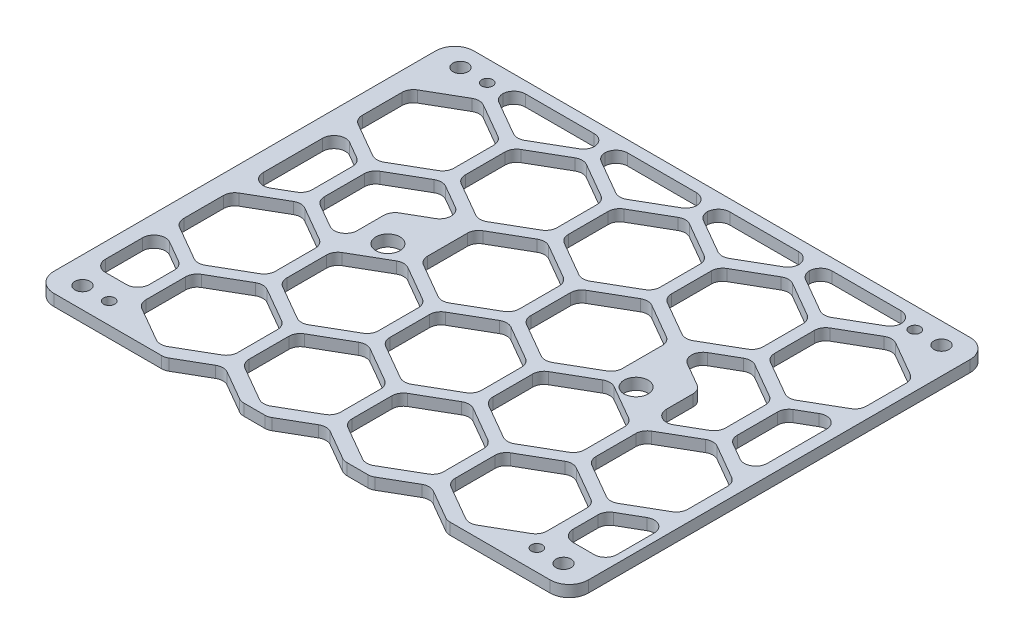
SolidWorks part; units mm, degrees
material "A-玻璃纤维"
ref_plane "前视基准面" through (0, 0, 0) normal (0, 0, 1) x (1, 0, 0)
ref_plane "上视基准面" through (0, 0, 0) normal (0, 1, 0) x (1, 0, 0)
ref_plane "右视基准面" through (0, 0, 0) normal (1, 0, 0) x (0, 0, -1)
other "Configuration Table"
sketch "草图1" plane through (0, 0, 0) normal (0, 1, 0) x (1, 0, 0)
  line L0 (-63, 49.5) -> (-63, -30.5) construction
  line L1 (-56, -49.5) -> (56, -49.5) construction
  line L2 (-56, -49.5) -> (-56, 49.5) construction
  line L3 (-56, 49.5) -> (56, 49.5) construction
  line L4 (56, -49.5) -> (56, 49.5) construction
  line L5 (-56, -49.5) -> (56, 49.5) construction
  line L6 (-56, 49.5) -> (56, -49.5) construction
  line L7 (-59.25, -36.5) -> (59.25, -36.5) construction
  line L8 (-59.25, -36.5) -> (-59.25, 36.5) construction
  line L9 (-59.25, 36.5) -> (59.25, 36.5) construction
  line L10 (59.25, -36.5) -> (59.25, 36.5) construction
  line L11 (-59.25, -36.5) -> (59.25, 36.5) construction
  line L12 (-59.25, 36.5) -> (59.25, -36.5) construction
  line L13 (-70, -55) -> (70, -55)
  line L14 (-70, -55) -> (-70, 55)
  line L15 (-70, 55) -> (70, 55)
  line L16 (70, -55) -> (70, 55) construction
  line L17 (-70, -55) -> (70, 55) construction
  line L18 (-70, 55) -> (70, -55) construction
  line L19 (63, -49.5) -> (-63, -49.5) construction
  line L20 (63, -49.5) -> (63, 49.5) construction
  line L21 (63, 49.5) -> (-63, 49.5) construction
  line L22 (-63, -49.5) -> (-63, 49.5) construction
  line L23 (63, -49.5) -> (-63, 49.5) construction
  line L24 (63, 49.5) -> (-63, -49.5) construction
  line L25 (70, 55) -> (120, 55) construction
  line L26 (120, 55) -> (120, -55) construction
  line L27 (120, -55) -> (70, -55) construction
  line L28 (70, 55) -> (70, -55)
  circle A0 centre (-63, 49.5) radius 1.975
  circle A1 centre (63, 49.5) radius 1.975
  circle A2 centre (63, -49.5) radius 1.975
  circle A3 centre (-63, -49.5) radius 1.975
  circle A4 centre (-56, 49.5) radius 1.45
  circle A5 centre (56, 49.5) radius 1.45
  circle A6 centre (56, -49.5) radius 1.45
  circle A7 centre (-56, -49.5) radius 1.45
  circle A8 centre (-63, -30.5) radius 1.975 construction
  circle A9 centre (63, -30.5) radius 1.975 construction
  point P0 (0, 0)
  point P6 (0, 0)
  point P11 (0, 0)
  point P16 (0, 0)
  dimension "D8" = 3.95
  dimension "D9" = 2.9
  dimension "D1" = 112
  dimension "D2" = 99
  dimension "D3" = 73
  dimension "D4" = 118.5
  dimension "D5" = 140
  dimension "D6" = 110
  dimension "D7" = 126
  dimension "D11" = 80
  dimension "D12" = 50
  dimension "D10" = 2
extrude "凸台-拉伸1" add sketch "草图1" along normal mid plane 3
fillet "圆角1" radius 5 4 edges at (-70, 0, 55) (-70, 0, -55) (70, 0, 55) (70, 0, -55)
sketch "草图2" plane through (0, 1.5, 0) normal (0, 1, 0) x (1, 0, 0)
  line L0 (0, 0) -> (75, 0) construction
  line L2 (75, -25) -> (105, -25) construction
  line L3 (75, -25) -> (75, 25) construction
  line L4 (75, 25) -> (105, 25) construction
  line L5 (105, -25) -> (105, 25) construction
  line L6 (75, -25) -> (105, 25) construction
  line L7 (75, 25) -> (105, -25) construction
  circle A0 centre (0, 0) radius 45 construction
  circle A1 centre (75, 25) radius 1.65
  circle A2 centre (75, -25) radius 1.65
  circle A3 centre (105, 25) radius 1.65
  circle A4 centre (105, -25) radius 1.65
  dimension "D1" = 90
  dimension "D5" = 3.3
  dimension "D2" = 30
  dimension "D3" = 50
  dimension "D4" = 75
extrude "切除-拉伸1" [suppressed] cut sketch "草图2" against normal through all
sketch "草图3" plane through (0, 1.5, 0) normal (0, 1, 0) x (1, 0, 0)
  line L0 (-32.5, 0) -> (32.5, 0) construction
  circle A0 centre (-32.5, 0) radius 3.15
  circle A1 centre (32.5, 0) radius 3.15
  point P4 (0, 0)
  dimension "D2" = 6.3
  dimension "D1" = 65
extrude "切除-拉伸2" cut sketch "草图3" against normal through all
sketch "草图4" plane through (0, 1.5, 0) normal (0, 1, 0) x (1, 0, 0)
  line L0 (-70, 50) -> (-70, -50) construction
  line L1 (-53, 44.8564) -> (-65, 37.9282)
  line L2 (-65, 37.9282) -> (-65, 24.0718)
  line L3 (-65, 24.0718) -> (-53, 17.1436)
  line L4 (-53, 17.1436) -> (-41, 24.0718)
  line L5 (-41, 24.0718) -> (-41, 37.9282)
  line L6 (-41, 37.9282) -> (-53, 44.8564)
  line L7 (65, 55) -> (-65, 55) construction
  line L8 (-26, 44.8564) -> (-38, 37.9282)
  line L9 (-38, 37.9282) -> (-38, 24.0718)
  line L10 (-38, 24.0718) -> (-26, 17.1436)
  line L11 (-26, 17.1436) -> (-14, 24.0718)
  line L12 (-14, 24.0718) -> (-14, 37.9282)
  line L13 (-14, 37.9282) -> (-26, 44.8564)
  line L14 (1, 44.8564) -> (-11, 37.9282)
  line L15 (-11, 37.9282) -> (-11, 24.0718)
  line L16 (-11, 24.0718) -> (1, 17.1436)
  line L17 (1, 17.1436) -> (13, 24.0718)
  line L18 (13, 24.0718) -> (13, 37.9282)
  line L19 (13, 37.9282) -> (1, 44.8564)
  line L20 (28, 44.8564) -> (16, 37.9282)
  line L21 (16, 37.9282) -> (16, 24.0718)
  line L22 (16, 24.0718) -> (28, 17.1436)
  line L23 (28, 17.1436) -> (40, 24.0718)
  line L24 (40, 24.0718) -> (40, 37.9282)
  line L25 (40, 37.9282) -> (28, 44.8564)
  line L26 (55, 44.8564) -> (43, 37.9282)
  line L27 (43, 37.9282) -> (43, 24.0718)
  line L28 (43, 24.0718) -> (55, 17.1436)
  line L29 (55, 17.1436) -> (67, 24.0718)
  line L30 (67, 24.0718) -> (67, 37.9282)
  line L31 (67, 37.9282) -> (55, 44.8564)
  line L32 (-26, -1.9136) -> (-38, -8.8418)
  line L33 (-38, -8.8418) -> (-38, -22.6982)
  line L34 (-38, -22.6982) -> (-26, -29.6264)
  line L35 (-26, -29.6264) -> (-14, -22.6982)
  line L36 (-14, -22.6982) -> (-14, -8.8418)
  line L37 (-14, -8.8418) -> (-26, -1.9136)
  line L38 (1, -1.9136) -> (-11, -8.8418)
  line L39 (-11, -8.8418) -> (-11, -22.6982)
  line L40 (-11, -22.6982) -> (1, -29.6264)
  line L41 (1, -29.6264) -> (13, -22.6982)
  line L42 (13, -22.6982) -> (13, -8.8418)
  line L43 (13, -8.8418) -> (1, -1.9136)
  line L44 (28, -1.9136) -> (16, -8.8418)
  line L45 (16, -8.8418) -> (16, -22.6982)
  line L46 (16, -22.6982) -> (28, -29.6264)
  line L47 (28, -29.6264) -> (40, -22.6982)
  line L48 (40, -22.6982) -> (40, -8.8418)
  line L49 (40, -8.8418) -> (28, -1.9136)
  line L50 (55, -1.9136) -> (43, -8.8418)
  line L51 (43, -8.8418) -> (43, -22.6982)
  line L52 (43, -22.6982) -> (55, -29.6264)
  line L53 (55, -29.6264) -> (67, -22.6982)
  line L54 (67, -22.6982) -> (67, -8.8418)
  line L55 (67, -8.8418) -> (55, -1.9136)
  line L56 (-53, -1.9136) -> (-65, -8.8418)
  line L57 (-65, -8.8418) -> (-65, -22.6982)
  line L58 (-65, -22.6982) -> (-53, -29.6264)
  line L59 (-53, -29.6264) -> (-41, -22.6982)
  line L60 (-41, -22.6982) -> (-41, -8.8418)
  line L61 (-41, -8.8418) -> (-53, -1.9136)
  line L62 (-53, 44.8564) -> (-26, 44.8564) construction
  line L63 (-53, 44.8564) -> (-53, -1.9136) construction
  line L64 (-53, 31) -> (-47, 20.6077) construction
  line L65 (-39.5, 21.4737) -> (-51.5, 14.5455) construction
  line L66 (-51.5, 14.5455) -> (-51.5, 0.6891) construction
  line L67 (-51.5, 0.6891) -> (-39.5, -6.2391) construction
  line L68 (-39.5, -6.2391) -> (-27.5, 0.6891) construction
  line L69 (-27.5, 0.6891) -> (-27.5, 14.5455) construction
  line L70 (-27.5, 14.5455) -> (-39.5, 21.4737) construction
  line L71 (-53, 44.8564) -> (-39.5, 21.4737) construction
  line L72 (-12.5, 21.4737) -> (-24.5, 14.5455)
  line L73 (-24.5, 14.5455) -> (-24.5, 0.6891)
  line L74 (-24.5, 0.6891) -> (-12.5, -6.2391)
  line L75 (-12.5, -6.2391) -> (-0.5, 0.6891)
  line L76 (-0.5, 0.6891) -> (-0.5, 14.5455)
  line L77 (-0.5, 14.5455) -> (-12.5, 21.4737)
  line L78 (14.5, 21.4737) -> (2.5, 14.5455)
  line L79 (2.5, 14.5455) -> (2.5, 0.6891)
  line L80 (2.5, 0.6891) -> (14.5, -6.2391)
  line L81 (14.5, -6.2391) -> (26.5, 0.6891)
  line L82 (26.5, 0.6891) -> (26.5, 14.5455)
  line L83 (26.5, 14.5455) -> (14.5, 21.4737)
  line L84 (41.5, 21.4737) -> (29.5, 14.5455) construction
  line L85 (29.5, 14.5455) -> (29.5, 0.6891) construction
  line L86 (29.5, 0.6891) -> (41.5, -6.2391) construction
  line L87 (41.5, -6.2391) -> (53.5, 0.6891) construction
  line L88 (53.5, 0.6891) -> (53.5, 14.5455) construction
  line L89 (53.5, 14.5455) -> (41.5, 21.4737) construction
  line L90 (-12.5, -25.2963) -> (-24.5, -32.2245)
  line L91 (-24.5, -32.2245) -> (-24.5, -46.0809)
  line L92 (-24.5, -46.0809) -> (-12.5, -53.0091)
  line L93 (-12.5, -53.0091) -> (-0.5, -46.0809)
  line L94 (-0.5, -46.0809) -> (-0.5, -32.2245)
  line L95 (-0.5, -32.2245) -> (-12.5, -25.2963)
  line L96 (14.5, -25.2963) -> (2.5, -32.2245)
  line L97 (2.5, -32.2245) -> (2.5, -46.0809)
  line L98 (2.5, -46.0809) -> (14.5, -53.0091)
  line L99 (14.5, -53.0091) -> (26.5, -46.0809)
  line L100 (26.5, -46.0809) -> (26.5, -32.2245)
  line L101 (26.5, -32.2245) -> (14.5, -25.2963)
  line L102 (41.5, -25.2963) -> (29.5, -32.2245)
  line L103 (29.5, -32.2245) -> (29.5, -46.0809)
  line L104 (29.5, -46.0809) -> (41.5, -53.0091)
  line L105 (41.5, -53.0091) -> (53.5, -46.0809)
  line L106 (53.5, -46.0809) -> (53.5, -32.2245)
  line L107 (53.5, -32.2245) -> (41.5, -25.2963)
  line L108 (-39.5, -25.2963) -> (-51.5, -32.2245)
  line L109 (-51.5, -32.2245) -> (-51.5, -46.0809)
  line L110 (-51.5, -46.0809) -> (-39.5, -53.0091)
  line L111 (-39.5, -53.0091) -> (-27.5, -46.0809)
  line L112 (-27.5, -46.0809) -> (-27.5, -32.2245)
  line L113 (-27.5, -32.2245) -> (-39.5, -25.2963)
  line L114 (-39.5, 21.4737) -> (-12.5, 21.4737) construction
  line L115 (-39.5, 21.4737) -> (-39.5, -25.2963) construction
  line L116 (-27.5, 14.5455) -> (-39.5, 7.6173)
  line L117 (-39.5, 7.6173) -> (-39.5, -6.2391)
  line L118 (29.5, 14.5455) -> (41.5, 7.6173)
  line L119 (41.5, 7.6173) -> (41.5, -6.2391)
  line L120 (41.5, -6.2391) -> (53.5, 0.6891)
  line L121 (53.5, 0.6891) -> (53.5, 14.5455)
  line L122 (53.5, 14.5455) -> (41.5, 21.4737)
  line L123 (41.5, 21.4737) -> (29.5, 14.5455)
  line L124 (-27.5, 14.5455) -> (-39.5, 21.4737)
  line L125 (-39.5, 21.4737) -> (-51.5, 14.5455)
  line L126 (-51.5, 14.5455) -> (-51.5, 0.6891)
  line L127 (-51.5, 0.6891) -> (-39.5, -6.2391)
  line L128 (-65, 20.5718) -> (-54.6825, 14.615)
  line L129 (-54.6825, 14.615) -> (-54.6825, 0.615)
  line L130 (-54.6825, 0.615) -> (-65, -5.3418)
  line L131 (-65, -5.3418) -> (-65, 20.5718)
  line L132 (1, -982.8564) -> (1, 49017.1436) construction
  line L133 (56.6825, 0.615) -> (67, -5.3418)
  line L134 (56.6825, 14.615) -> (56.6825, 0.615)
  line L135 (67, 20.5718) -> (56.6825, 14.615)
  line L136 (67, -5.3418) -> (67, 20.5718)
  line L137 (-66, -25.585) -> (-66, -43.5)
  line L138 (-66, -43.5) -> (-54.5, -43.5)
  line L139 (-54.5, -43.5) -> (-54.5, -32.2245)
  line L140 (-54.5, -32.2245) -> (-66, -25.585)
  line L141 (56.5, -43.5) -> (56.5, -32.2245)
  line L142 (68, -43.5) -> (56.5, -43.5)
  line L143 (68, -25.585) -> (68, -43.5)
  line L144 (56.5, -32.2245) -> (68, -25.585)
  line L145 (-51.5, 52) -> (-51.5, 47.4545)
  line L146 (-51.5, 47.4545) -> (-39.5, 40.5263)
  line L147 (-39.5, 40.5263) -> (-27.5, 47.4545)
  line L148 (-27.5, 47.4545) -> (-27.5, 52)
  line L149 (-27.5, 52) -> (-51.5, 52)
  line L150 (-0.725, 52) -> (-24.725, 52)
  line L151 (-24.725, 52) -> (-24.725, 47.4545)
  line L152 (-24.725, 47.4545) -> (-12.725, 40.5263)
  line L153 (-12.725, 40.5263) -> (-0.725, 47.4545)
  line L154 (-0.725, 47.4545) -> (-0.725, 52)
  line L155 (26.05, 52) -> (2.05, 52)
  line L156 (2.05, 52) -> (2.05, 47.4545)
  line L157 (2.05, 47.4545) -> (14.05, 40.5263)
  line L158 (14.05, 40.5263) -> (26.05, 47.4545)
  line L159 (26.05, 47.4545) -> (26.05, 52)
  line L160 (52.825, 52) -> (28.825, 52)
  line L161 (28.825, 52) -> (28.825, 47.4545)
  line L162 (28.825, 47.4545) -> (40.825, 40.5263)
  line L163 (40.825, 40.5263) -> (52.825, 47.4545)
  line L164 (52.825, 47.4545) -> (52.825, 52)
  line L165 (-35.9484, -55) -> (-26, -49.2563)
  line L166 (-65, -55) -> (65, -55) construction
  line L167 (-26, -49.2563) -> (-16.0516, -55)
  line L168 (-16.0516, -55) -> (-35.9484, -55)
  line L169 (10.9484, -55) -> (-8.9484, -55)
  line L170 (-8.9484, -55) -> (1, -49.2563)
  line L171 (1, -49.2563) -> (10.9484, -55)
  line L172 (37.9484, -55) -> (18.0516, -55)
  line L173 (18.0516, -55) -> (28, -49.2563)
  line L174 (28, -49.2563) -> (37.9484, -55)
  circle A0 centre (-53, 31) radius 12 construction
  circle A1 centre (-63, -49.5) radius 1.975 construction
  dimension "D1" = 24
  dimension "D3" = 24
  dimension "D2" = 5
  dimension "D6" = 90
  dimension "D7" = 27
  dimension "D8" = 46.77
  dimension "D10" = 27
  dimension "D13" = 14
  dimension "D14" = 27
  dimension "D15" = 46.77
  dimension "D16" = 3.5
  dimension "D17" = 3.5
  dimension "D18" = 4
  dimension "D19" = 3
  dimension "D20" = 3
  dimension "D21" = 6
  dimension "D22" = 3
  dimension "D23" = 3
  dimension "D24" = 4
  dimension "D25" = 26.775
  dimension "D26" = 3
  dimension "D27" = 3.5
  dimension "D28" = 3.5
  dimension "D4" = 5
  dimension "D5" = 2
  dimension "D9" = 2
  dimension "D11" = 4
  dimension "D12" = 2
  dimension "D29" = 3
extrude "切除-拉伸3" cut sketch "草图4" against normal through all
fillet "圆角2" radius 3 144 edges at (-41, 0, -24.0718) (-53, 0, -17.1436) (-65, 0, -24.0718) (-65, 0, -37.9282) (-41, 0, -37.9282) (-0.5, 0, 46.0809) (-12.5, 0, 53.0091) (-24.5, 0, 46.0809) (-24.5, 0, 32.2245) (-12.5, 0, 25.2963) (-0.5, 0, 32.2245) (26.5, 0, -0.6891) (14.5, 0, 6.2391) (2.5, 0, -0.6891) (2.5, 0, -14.5455) (14.5, 0, -21.4737) (26.5, 0, -14.5455) (-0.5, 0, -0.6891) (-12.5, 0, 6.2391) (-24.5, 0, -0.6891) (-24.5, 0, -14.5455) (-12.5, 0, -21.4737) (-0.5, 0, -14.5455) (-41, 0, 22.6982) (-53, 0, 29.6264) (-65, 0, 22.6982) (-65, 0, 8.8418) (-53, 0, 1.9136) (-41, 0, 8.8418) (26.5, 0, 46.0809) (14.5, 0, 53.0091) (2.5, 0, 46.0809) (2.5, 0, 32.2245) (14.5, 0, 25.2963) (26.5, 0, 32.2245) (67, 0, 22.6982) (55, 0, 29.6264) (43, 0, 22.6982) (43, 0, 8.8418) (55, 0, 1.9136) (67, 0, 8.8418) (40, 0, 22.6982) (28, 0, 29.6264) (16, 0, 22.6982) (16, 0, 8.8418) (28, 0, 1.9136) (40, 0, 8.8418) (13, 0, 22.6982) (1, 0, 29.6264) (-11, 0, 22.6982) (-11, 0, 8.8418) (1, 0, 1.9136) (13, 0, 8.8418) (-14, 0, 22.6982) (-26, 0, 29.6264) (-38, 0, 22.6982) (-38, 0, 8.8418) (-26, 0, 1.9136) (-14, 0, 8.8418) (67, 0, -24.0718) (55, 0, -17.1436) (43, 0, -24.0718) (43, 0, -37.9282) (55, 0, -44.8564) (67, 0, -37.9282) (40, 0, -24.0718) (28, 0, -17.1436) (16, 0, -24.0718) (16, 0, -37.9282) (28, 0, -44.8564) (40, 0, -37.9282) (13, 0, -24.0718) (1, 0, -17.1436) (-11, 0, -24.0718) (-11, 0, -37.9282) (1, 0, -44.8564) (13, 0, -37.9282) (-14, 0, -24.0718) (-26, 0, -17.1436) (-38, 0, -24.0718) (-38, 0, -37.9282) (-26, 0, -44.8564) (-14, 0, -37.9282) (-53, 0, -44.8564) (53.5, 0, 46.0809) (41.5, 0, 53.0091) (29.5, 0, 32.2245) (41.5, 0, 25.2963) (53.5, 0, 32.2245) (29.5, 0, 46.0809) (-27.5, 0, 46.0809) (-39.5, 0, 53.0091) (-51.5, 0, 32.2245) (-39.5, 0, 25.2963) (-27.5, 0, 32.2245) (-51.5, 0, 46.0809) (-54.5, 0, 43.5) (-66, 0, 43.5) (-66, 0, 25.585) (-54.5, 0, 32.2245) (67, 0, -20.5718) (67, 0, 5.3418) (56.6825, 0, -0.615) (56.6825, 0, -14.615) (56.5, 0, 32.2245) (68, 0, 25.585) (68, 0, 43.5) (56.5, 0, 43.5) (-54.6825, 0, -14.615) (-54.6825, 0, -0.615) (-65, 0, 5.3418) (-65, 0, -20.5718) (-51.5, 0, -0.6891) (-51.5, 0, -14.5455) (-27.5, 0, -14.5455) (-39.5, 0, -7.6173) (-39.5, 0, 6.2391) (29.5, 0, -14.5455) (41.5, 0, -21.4737) (53.5, 0, -14.5455) (53.5, 0, -0.6891) (41.5, 0, 6.2391) (41.5, 0, -7.6173) (-39.5, 0, -21.4737) (-27.5, 0, -47.4545) (-39.5, 0, -40.5263) (-51.5, 0, -47.4545) (-27.5, 0, -52) (-0.725, 0, -52) (-0.725, 0, -47.4545) (-12.725, 0, -40.5263) (-24.725, 0, -47.4545) (-24.725, 0, -52) (26.05, 0, -52) (26.05, 0, -47.4545) (14.05, 0, -40.5263) (2.05, 0, -47.4545) (2.05, 0, -52) (52.825, 0, -52) (52.825, 0, -47.4545) (40.825, 0, -40.5263) (28.825, 0, -47.4545) (28.825, 0, -52) (-51.5, 0, -52)
fillet "圆角3" radius 3 9 edges at (37.9484, 0, 55) (-26, 0, 49.2563) (-16.0516, 0, 55) (-8.9484, 0, 55) (1, 0, 49.2563) (10.9484, 0, 55) (18.0516, 0, 55) (28, 0, 49.2563) (-35.9484, 0, 55)
